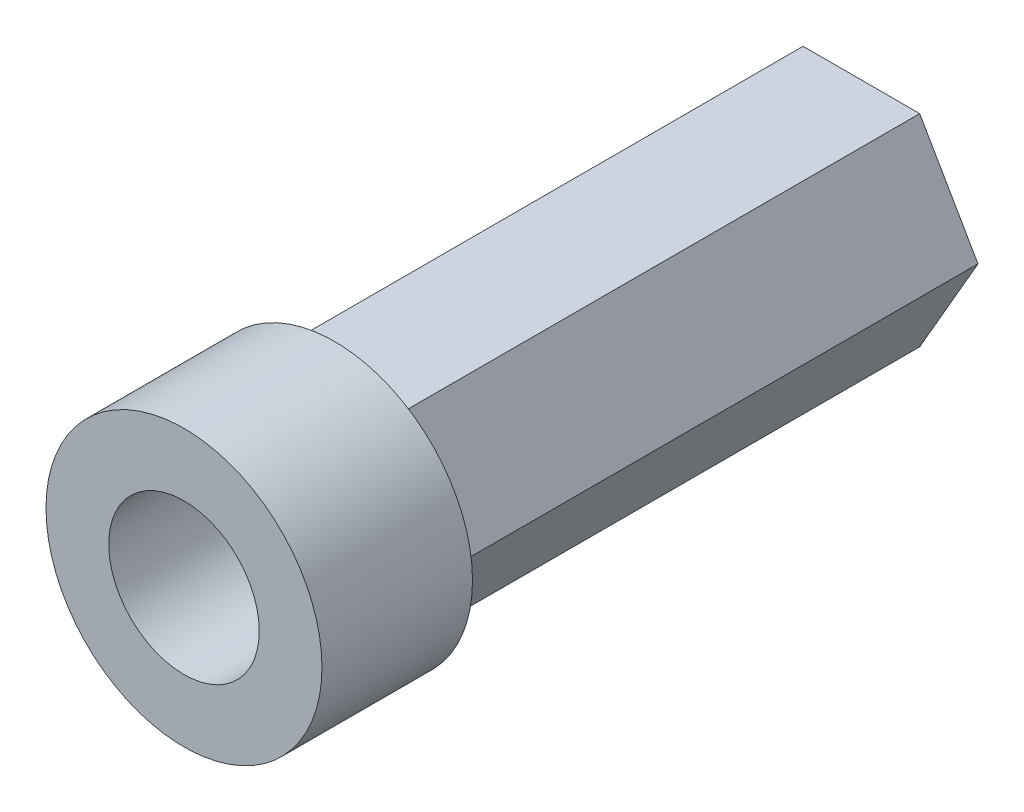
SolidWorks part; units mm, degrees
ref_plane "前视基准面" through (0, 0, 0) normal (0, 0, 1) x (1, 0, 0)
ref_plane "上视基准面" through (0, 0, 0) normal (0, 1, 0) x (1, 0, 0)
ref_plane "右视基准面" through (0, 0, 0) normal (1, 0, 0) x (0, 0, -1)
sketch "草图1" plane through (0, 0, 0) normal (0, 0, 1) x (1, 0, 0)
  line L1 (-2.3238, 4.025) -> (-4.6477, 0)
  line L2 (-4.6477, 0) -> (-2.3238, -4.025)
  line L3 (-2.3238, -4.025) -> (2.3238, -4.025)
  line L4 (2.3238, -4.025) -> (4.6477, 0)
  line L5 (4.6477, 0) -> (2.3238, 4.025)
  line L6 (2.3238, 4.025) -> (-2.3238, 4.025)
  circle A0 centre (0, 0) radius 4.025 construction
  circle A1 centre (0, 0) radius 3
  circle A2 centre (0, 0) radius 5.5
  dimension "D2" = 6
  dimension "D3" = 11
  dimension "D1" = 8.05
extrude "凸台-拉伸1" add sketch "草图1" along normal blind 6 contours L5 L6 L1 L2 L3 L4 A2 | A2 A1 region at (0, 3.902, 0) region at (-5.3444, 0, 0)
extrude "凸台-拉伸2" add sketch "草图1<3>" against normal blind 21 contours L5 L6 L1 L2 L3 L4 A1 region at (0, 3.902, 0)
sketch "草图1<3>" plane through (0, 0, 0) normal (0, 0, 1) x (1, 0, 0) same geometry as "草图1"
